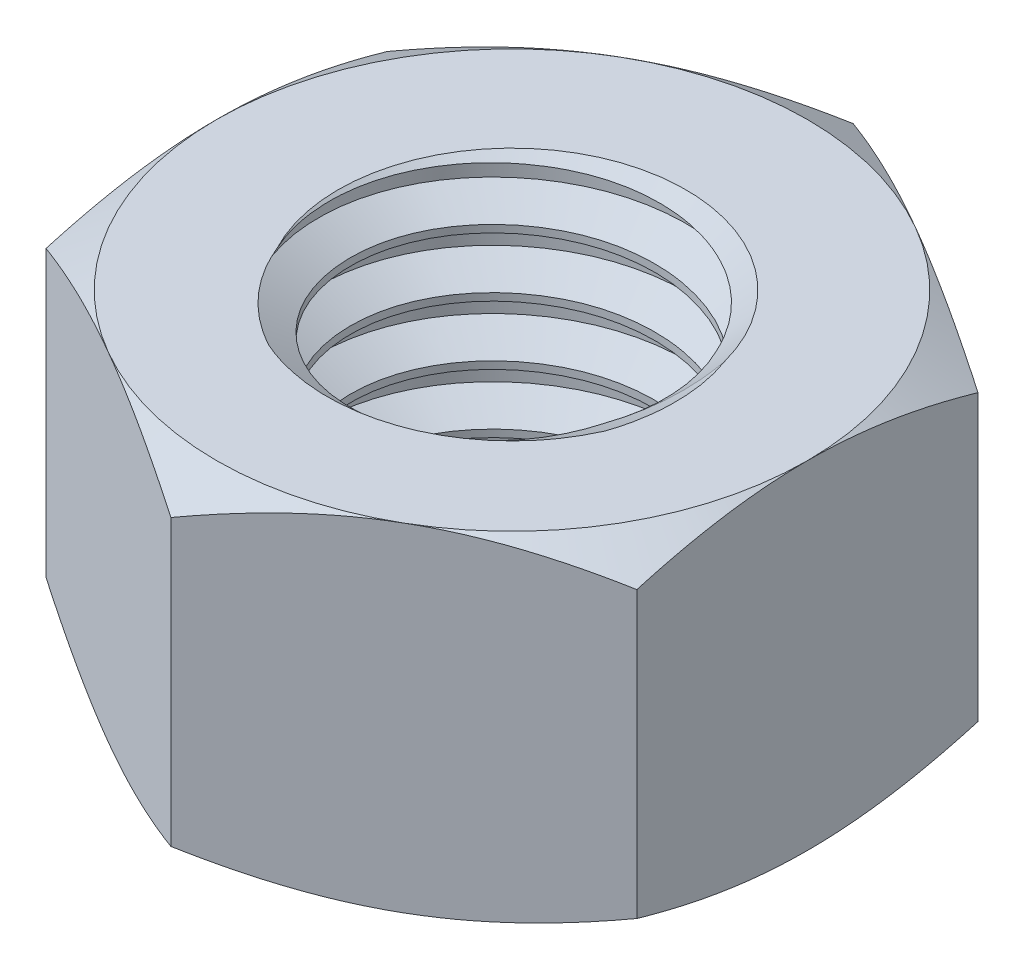
SolidWorks part; units mm, degrees
ref_plane "Piano frontale" through (0, 0, 0) normal (0, 0, 1) x (1, 0, 0)
ref_plane "Piano superiore" through (0, 0, 0) normal (0, 1, 0) x (1, 0, 0)
ref_plane "Piano destro" through (0, 0, 0) normal (1, 0, 0) x (0, 0, -1)
sketch "Schizzo1" plane through (0, 0, 0) normal (0, 1, 0) x (1, 0, 0)
  line L1 (0, 4.0415) -> (-3.5, 2.0207)
  line L2 (-3.5, 2.0207) -> (-3.5, -2.0207)
  line L3 (-3.5, -2.0207) -> (0, -4.0415)
  line L4 (0, -4.0415) -> (3.5, -2.0207)
  line L5 (3.5, -2.0207) -> (3.5, 2.0207)
  line L6 (3.5, 2.0207) -> (0, 4.0415)
  circle A0 centre (0, 0) radius 4.0415 construction
  dimension "D1" = 7
  dimension "D2" = 8.0829
extrude "Estrusione-Estrusione1" add sketch "Schizzo1" along normal blind 4
sketch "Schizzo3" plane through (0, 4, 0) normal (0, 1, 0) x (1, 0, 0)
  circle A0 centre (0, 0) radius 1.81
extrude "Taglio-Estrusione1" cut sketch "Schizzo3" against normal through all
chamfer "Smusso2" distance 0.25 angle 40 2 edges at (0, 4, 1.81) (0, 0, 1.81) first distance on face at (0, 4, 1.81) first distance on face at (0, 0, 1.81)
thread "Filettatura1" pitch 0.7 method cut profile "Profilo filettatura1" start angle 0, offset 1, length 0, pitch 0.7, diameter 3.62
ref_plane "Piano1" through (-1.81, 4.7902, 0) normal (0, 0, 1) x (-1, 0, 0)
sketch "Profilo filettatura1" plane through (-1.81, 4.7902, 0) normal (0, 0, 1) x (-1, 0, 0)
  line L0 (0, 0) -> (0, 0.7) construction
  line L11 (0, 0.6125) -> (0, 0)
  line L12 (0, 0) -> (0.3789, 0.2188)
  line L13 (0.3789, 0.2188) -> (0.3789, 0.3938)
  line L15 (0.3789, 0.3938) -> (0, 0.6125)
  line L17 (0.3789, 0.3063) -> (0, 0.3063) construction
  point P3 (0, 0)
  dimension "Pitch" = 0.7
  dimension "Profile_Angle" = 60
  dimension "Profile_Land" = 0.175
  dimension "Profile_Height" = 0.3789
sketch "Schizzo4" plane through (0, 0, 0) normal (0, 1, 0) x (1, 0, 0)
  circle A0 centre (0, 0) radius 3.5 construction
sketch "Schizzo5" plane through (0, 0, 0) normal (1, 0, 0) x (0, 0, -1)
  line L1 (-3.5, 0) -> (-4.0415, 0)
  line L2 (-4.0415, 0) -> (-2.0207, 0) construction
  line L3 (3.5, 0) -> (-3.5, 0) construction
  line L4 (-4.0415, 0) -> (-4.0415, 0.3126)
  line L5 (-4.0415, 4) -> (-4.0415, 0) construction
  line L6 (-4.0415, 0.3126) -> (-3.5, 0)
  line L7 (0, 0) -> (0, 4) construction
  line L8 (-2.0207, 4) -> (2.0207, 4) construction
  line L9 (-4.0415, 2) -> (4.0415, 2) construction
  line L10 (4.0415, 4) -> (4.0415, 0) construction
  line L11 (-3.5, 4) -> (-4.0415, 4)
  line L12 (-4.0415, 4) -> (-4.0415, 3.6874)
  line L13 (-4.0415, 3.6874) -> (-3.5, 4)
  dimension "D1" = 30
revolve "Taglia-Rivoluzione1" cut sketch "Schizzo5" angle 360 about L7
scale "Scale1" scale about centroid uniform scaling yes scale factor 1.25
